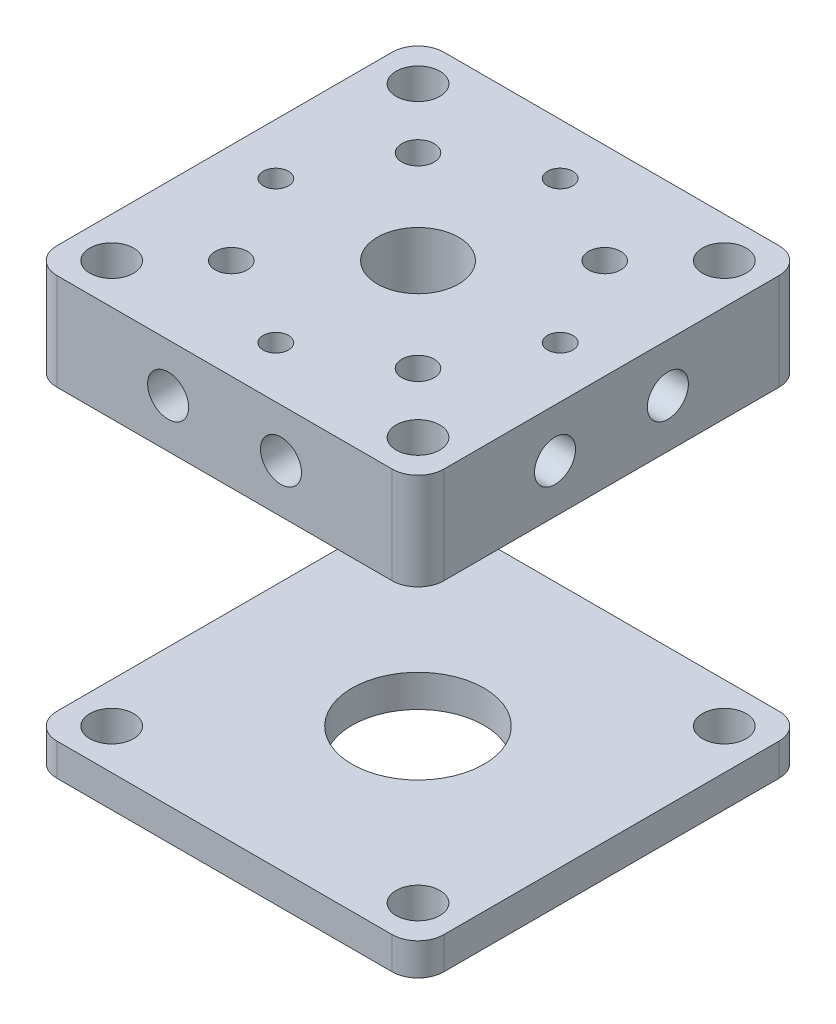
SolidWorks part; units mm, degrees
material "Alum Plate"
ref_plane "Front Plane" through (0, 0, 0) normal (0, 0, 1) x (1, 0, 0)
ref_plane "Top Plane" through (0, 0, 0) normal (0, 1, 0) x (1, 0, 0)
ref_plane "Right Plane" through (0, 0, 0) normal (1, 0, 0) x (0, 0, -1)
other "Bounding Box"
ref_plane "Default Plane" through (-8.9266, -12.7485, 0) normal (-0.1736, 0.9848, 0) x (0.9848, 0.1736, 0)
sketch "Sketch1" plane through (0, 0, 0) normal (0, 1, 0) x (1, 0, 0)
  line L0 (0, -12.5) -> (0, 12.5) construction
  line L1 (-14, 0) -> (0, 14) construction
  line L2 (-19.05, 19.05) -> (19.05, 19.05)
  line L3 (-19.05, 19.05) -> (-19.05, -19.05)
  line L4 (-19.05, -19.05) -> (19.05, -19.05)
  line L5 (19.05, 19.05) -> (19.05, -19.05)
  line L6 (-19.05, 19.05) -> (19.05, -19.05) construction
  line L7 (-19.05, -19.05) -> (19.05, 19.05) construction
  line L8 (9.1924, 9.1924) -> (-9.1924, 9.1924) construction
  line L9 (9.1924, 9.1924) -> (9.1924, -9.1924) construction
  line L10 (9.1924, -9.1924) -> (-9.1924, -9.1924) construction
  line L11 (-9.1924, 9.1924) -> (-9.1924, -9.1924) construction
  line L12 (9.1924, 9.1924) -> (-9.1924, -9.1924) construction
  line L13 (9.1924, -9.1924) -> (-9.1924, 9.1924) construction
  line L14 (-14, 0) -> (0, -14) construction
  line L15 (0, 14) -> (14, 0) construction
  line L16 (0, -14) -> (14, 0) construction
  line L17 (-14, 0) -> (14, 0) construction
  line L18 (0, 14) -> (0, -14) construction
  circle A0 centre (-15.24, 15.24) radius 1.3843 construction
  circle A1 centre (15.24, 15.24) radius 1.3843 construction
  circle A2 centre (15.24, -15.24) radius 1.3843 construction
  circle A3 centre (-15.24, -15.24) radius 1.3843 construction
  circle A4 centre (0, 0) radius 4
  circle A5 centre (9.1924, 9.1924) radius 1.5875
  circle A6 centre (9.1924, -9.1924) radius 1.5875
  circle A7 centre (-9.1924, -9.1924) radius 1.5875
  circle A8 centre (-9.1924, 9.1924) radius 1.5875
  circle A9 centre (-14, 0) radius 1.25
  circle A10 centre (0, 14) radius 1.25
  circle A11 centre (14, 0) radius 1.25
  circle A12 centre (0, -14) radius 1.25
  arc A13 (-9.8995, 9.8995) -> (0, 14) centre (0, 0) cw
  point P3 (0, 0)
  point P35 (0, 14.5587)
  point P37 (0, 0)
  circle B0 centre (-9.8995, -9.8995) radius 1.2645 construction
  circle B1 centre (0, -8) radius 1.5875 construction
  circle B2 centre (0, 0) radius 4 construction
  circle B3 centre (9.8995, 9.8995) radius 1.2645 construction
  circle B4 centre (0, 8) radius 1.5875 construction
  circle B5 centre (9.8995, -9.8995) radius 1.2645 construction
  circle B6 centre (0, -12.5) radius 1.5875 construction
  circle B7 centre (-9.5, 0) radius 1.5875 construction
  circle B8 centre (-15.24, 15.24) radius 1.3843 construction
  circle B9 centre (15.24, 15.24) radius 1.3843 construction
  circle B10 centre (15.24, -15.24) radius 1.3843 construction
  circle B11 centre (-15.24, -15.24) radius 1.3843 construction
  circle B12 centre (9.5, 0) radius 1.5875 construction
  circle B13 centre (-9.8995, 9.8995) radius 1.2645 construction
  circle B14 centre (0, 12.5) radius 1.5875 construction
  dimension "D2" = 3.175
  dimension "D4" = 2.5
  dimension "D1" = 38.1
  dimension "D3" = 26
sketch_block_instance "Block-36mm gearbox motor block holes-1"
sketch_block "Block-36mm gearbox motor block holes"
extrude "Boss-Extrude1" add sketch "Sketch1" along normal mid plane 9.525 contours L5 L2 L3 L4 A12 A11 A9 A8 A10 A7 A6 A5 A4 A3 A2 A1 A0 region at (0, 0, -18.5112)
sketch "Sketch4" plane through (0, 0, 19.05) normal (0, 0, 1) x (1, 0, 0)
  line L0 (-5.5562, 0) -> (0, 0) construction
  line L1 (0, 0) -> (5.5562, 0) construction
  circle A0 centre (-5.5562, 0) radius 2.0193
  circle A1 centre (5.5562, 0) radius 2.0193
  dimension "D2" = 4.0386
  dimension "D1" = 11.1125
extrude "Cut-Extrude2" cut sketch "Sketch4" against normal blind 9.525
sketch "Sketch7" plane through (0, -4.7625, 0) normal (0, -1, 0) x (1, 0, 0)
  line L0 (-19.05, 15.0813) -> (-15.0813, 15.0813) construction
  line L1 (-19.05, -19.05) -> (-19.05, 19.05) construction
  line L2 (-15.0813, 15.0813) -> (-15.0813, 19.05) construction
  line L3 (-19.05, 19.05) -> (19.05, 19.05) construction
  line L4 (0, 0) -> (-15.0813, 15.0813) construction
  line L5 (0, 0) -> (15.0813, 15.0812) construction
  circle A0 centre (-15.0813, 15.0813) radius 2.1526
  circle A1 centre (15.0813, 15.0812) radius 2.1527
  circle A2 centre (15.0812, -15.0813) radius 2.1527
  circle A3 centre (-15.0813, -15.0812) radius 2.1526
  point P9 (-14.2776, -15.8348)
  point P10 (0, 0)
  dimension "D2" = 4.3053
  dimension "D1" = 3.9688
  dimension "D4" = 90
  dimension "D3" = 4
extrude "Cut-Extrude3" cut sketch "Sketch7" against normal through all
pattern_circular "CirPattern1" count 4 over 360 about axis through (0, 4.7625, 0) along (0, -1, 0) of "Cut-Extrude2"
ref_plane "Plane1" through (0, -34.9377, 0) normal (0, -1, 0) x (-1, 0, 0)
sketch "Sketch6" plane through (0, -34.9377, 0) normal (0, -1, 0) x (-1, 0, 0)
  line L0 (19.05, 19.05) -> (-19.05, 19.05) construction
  line L1 (19.05, 19.05) -> (19.05, -19.05) construction
  line L2 (19.05, -19.05) -> (-19.05, -19.05) construction
  line L3 (-19.05, 19.05) -> (-19.05, -19.05) construction
  line L12 (19.05, 19.05) -> (-19.05, 19.05)
  line L13 (19.05, 19.05) -> (19.05, -19.05)
  line L14 (19.05, -19.05) -> (-19.05, -19.05)
  line L15 (-19.05, 19.05) -> (-19.05, -19.05)
  circle A8 centre (0, 0) radius 6.5
  circle A17 centre (-15.0812, 15.0813) radius 2.1526
  circle A18 centre (15.0813, 15.0812) radius 2.1526
  circle A19 centre (15.0813, -15.0813) radius 2.1527
  circle A20 centre (-15.0813, -15.0812) radius 2.1526
  circle A21 centre (-15.0812, 15.0813) radius 2.1527 construction
  dimension "D2" = 13
extrude "Boss-Extrude2" add sketch "Sketch6" along normal blind 3.175 separate body
fillet "Fillet1" radius 2.54 4 edges at (-19.05, 0, 19.05) (-19.05, 0, -19.05) (19.05, 0, -19.05) (19.05, 0, 19.05)
fillet "Fillet2" radius 2.54 4 edges at (-19.05, -36.5252, 19.05) (-19.05, -36.5252, -19.05) (19.05, -36.5252, -19.05) (19.05, -36.5252, 19.05)
